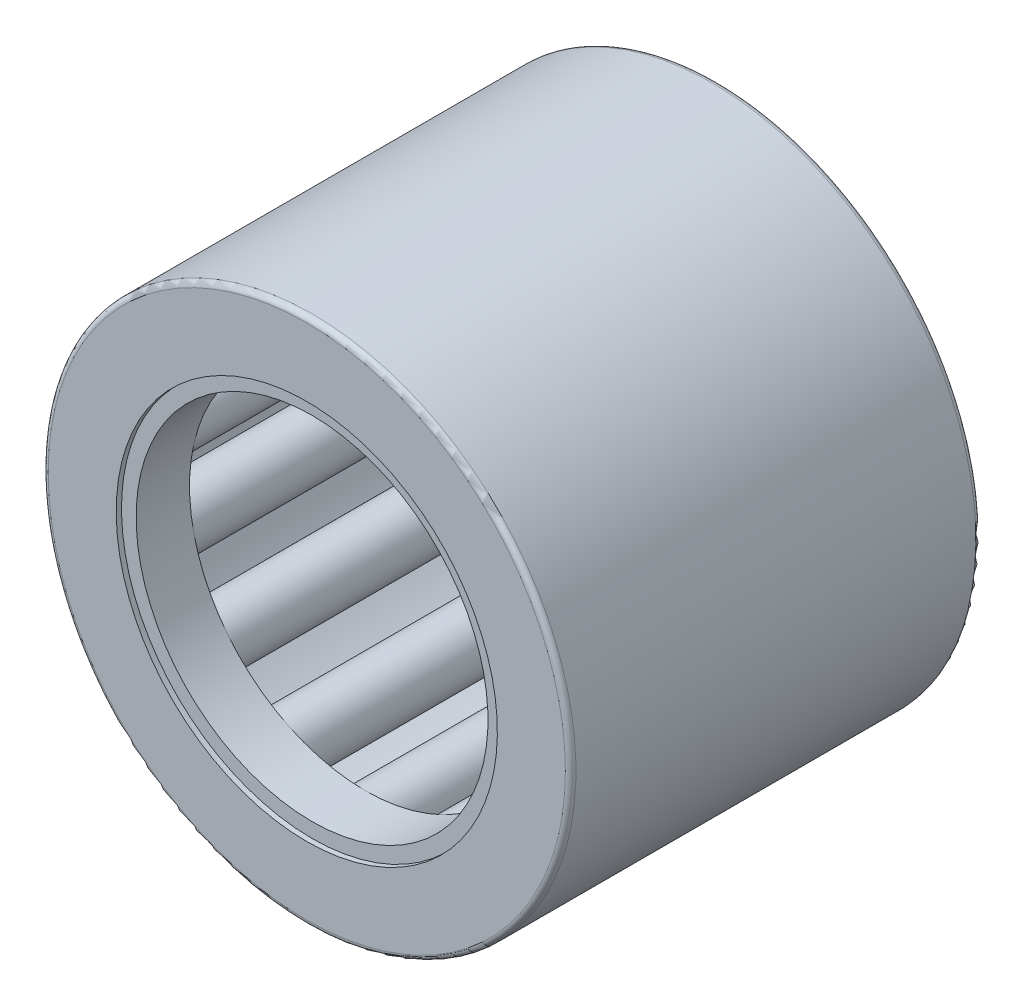
SolidWorks part; units mm, degrees
ref_plane "Front Plane" through (0, 0, 0) normal (0, 0, 1) x (1, 0, 0)
ref_plane "Top Plane" through (0, 0, 0) normal (0, 1, 0) x (1, 0, 0)
ref_plane "Right Plane" through (0, 0, 0) normal (1, 0, 0) x (0, 0, -1)
sketch "Sketch1" plane through (0, 0, 0) normal (1, 0, 0) x (0, 0, -1)
  line L0 (-7, 0) -> (7, 0) construction
  line L1 (0, 0) -> (0, 9) construction
  line L2 (-7, 0) -> (-7, 9) construction
  line L3 (-7, 9) -> (7, 9)
  line L4 (7, 9) -> (7, 0) construction
  line L5 (7, 0) -> (6, 0) construction
  line L6 (6, 0) -> (6, 8) construction
  line L7 (6, 8) -> (-6, 8)
  line L8 (-6, 8) -> (-6, 0) construction
  line L9 (-6, 0) -> (-7, 0) construction
  line L10 (-7, 9) -> (-7, 6.5)
  line L11 (-7, 6.5) -> (-6, 6.5)
  line L12 (-6, 6.5) -> (-6, 8)
  line L13 (6, 9) -> (6, 8) construction
  line L14 (6, 8) -> (6, 6.5)
  line L15 (6, 6.5) -> (7, 6.5)
  line L16 (7, 6.5) -> (7, 9)
  line L17 (6, 8) -> (6, 7) construction
  line L18 (6, 7) -> (6, 6) construction
  line L19 (6, -8) -> (6, -7) construction
  line L20 (6, -9) -> (6, -8) construction
  line L21 (7, -6.5) -> (7, -9) construction
  line L22 (6, -6.5) -> (7, -6.5) construction
  line L23 (6, -8) -> (6, -6.5) construction
  line L24 (-6, -6.5) -> (-6, -8) construction
  line L25 (-7, -6.5) -> (-6, -6.5) construction
  line L26 (-7, -9) -> (-7, -6.5) construction
  line L27 (6, -8) -> (-6, -8) construction
  line L28 (-7, -9) -> (7, -9) construction
  point P4 (0, 6)
  dimension "C | Width" = 14
  dimension "Fw | ID" = 12
  dimension "D | OD" = 18
sketch "Sketch7" plane through (0, 0, 0) normal (1, 0, 0) x (0, 0, -1)
  line L0 (-7, 9) -> (-7, 6.5) construction
  line L1 (-7, 6.5) -> (-6, 6.5) construction
  line L2 (-6, 6.5) -> (-6, 8) construction
  line L3 (6, 8) -> (-6, 8) construction
  line L4 (6, 8) -> (6, 6.5) construction
  line L5 (6, 6.5) -> (7, 6.5) construction
  line L6 (7, 6.5) -> (7, 9) construction
  line L8 (-7, 9) -> (7, 9) construction
  line L9 (-7, 9) -> (-7, 6.5)
  line L10 (-7, 6.5) -> (-6, 6.5)
  line L13 (-6, 6.5) -> (-6, 8)
  line L16 (6, 8) -> (-6, 8)
  line L17 (6, 8) -> (6, 6.5)
  line L18 (6, 6.5) -> (7, 6.5)
  line L19 (7, 6.5) -> (7, 9)
  line L20 (-7, 9) -> (7, 9)
revolve "Revolve1" add sketch "Sketch7" angle 360 about L0
sketch "Sketch2" plane through (0, 0, 0) normal (1, 0, 0) x (0, 0, -1)
  line L0 (-7, 6.5) -> (-6, 6.5) construction
  line L1 (-5, 7) -> (5, 7) construction
  line L2 (-5, 7) -> (-5, 8) construction
  line L3 (-5, 8) -> (5, 8)
  line L4 (5, 7) -> (5, 8) construction
  line L5 (6, 6.5) -> (7, 6.5) construction
  line L6 (-6, 7) -> (-5, 7) construction
  line L7 (5, 7) -> (6, 7) construction
  line L8 (7, 9) -> (7, 0) construction
  line L9 (-5, 7.25) -> (-5, 6.75) construction
  line L10 (-6, 7) -> (-6, 6.5) construction
  line L11 (-5, 8) -> (-5, 7.25)
  line L12 (5, 8) -> (5, 7.25)
  line L13 (5, 7.25) -> (-5, 7.25)
  line L14 (0, 8) -> (0, 6) construction
  line L16 (-5, 6.75) -> (-6, 6.75) construction
  line L17 (0, 0) -> (7, 0) construction
  line L18 (-5, -6.75) -> (-6, -6.75) construction
  line L19 (0, -8) -> (0, -6) construction
  line L20 (-6, -7) -> (-6, -6.5) construction
  line L21 (-5, -7.25) -> (-5, -6.75) construction
  line L22 (5, -7) -> (6, -7) construction
  line L23 (-6, -7) -> (-5, -7) construction
  line L24 (5, -7) -> (5, -8) construction
  line L25 (-5, -7) -> (-5, -8) construction
  line L26 (-5, -7) -> (5, -7) construction
  line L27 (5, -7.25) -> (-5, -7.25) construction
  line L28 (5, -8) -> (5, -7.25) construction
  line L29 (-5, -8) -> (-5, -7.25) construction
  line L30 (-5, -8) -> (5, -8) construction
  line L33 (6, 8) -> (-6, 8) construction
  line L34 (6, 8) -> (6, 6.5) construction
  line L35 (-6, 6.5) -> (-6, 8) construction
  line L36 (0, 0) -> (0, 9) construction
  point P16 (0, 7)
revolve "Revolve2" add sketch "Sketch2" angle 360 about L1
sketch "Sketch3" plane through (0, 0, 0) normal (1, 0, 0) x (0, 0, -1)
  line L1 (-6, 7) -> (6, 7)
  line L2 (-6, 7) -> (-6, 7.25)
  line L3 (-6, 7.25) -> (6, 7.25)
  line L4 (6, 7) -> (6, 7.25)
  line L5 (0, 0) -> (7, 0) construction
  line L7 (6, -7) -> (6, -7.25) construction
  line L8 (-6, -7.25) -> (6, -7.25) construction
  line L9 (-6, -7) -> (-6, -7.25) construction
  line L10 (-6, -7) -> (6, -7) construction
  line L11 (6, 8) -> (6, 6.5) construction
  line L12 (7, 9) -> (7, 0) construction
revolve "Revolve3" add sketch "Sketch3" angle 360 about L1
ref_axis "Axis1" through (0, 6.5, 7) along (0, 1, 0)
pattern_circular "CirPattern1" count 14 every 25.714 about axis through (0, 0, 7) along (0, 0, -1) of bodies 166 167
fillet "Fillet1" radius 0.18 2 edges at (0, -9, -7) (0, -9, 7)
sketch "Sketch4" plane through (0, 0, 0) normal (1, 0, 0) x (0, 0, -1)
  line L0 (5, 8) -> (5, 7.25) construction
  line L1 (6.82, 6) -> (5, 6)
  line L2 (6.82, 6) -> (6.82, 6.5)
  line L3 (6.82, 6.5) -> (5, 6.5)
  line L4 (5, 6) -> (5, 6.5)
  line L7 (6, 6.5) -> (7, 6.5) construction
  line L8 (6.82, -9) -> (6.82, 9) construction
revolve "Revolve4" add sketch "Sketch4" angle 360 about L0
sketch "Sketch5" plane through (0, 0, 0) normal (1, 0, 0) x (0, 0, -1)
  line L0 (-6.82, 9) -> (-6.82, -9) construction
  line L1 (-5, 6) -> (-6.82, 6)
  line L2 (-5, 6) -> (-5, 6.5)
  line L3 (-5, 6.5) -> (-6.82, 6.5)
  line L4 (-6.82, 6) -> (-6.82, 6.5)
  line L5 (-5, 8) -> (-5, 7.25) construction
  line L6 (-7, 6.5) -> (-6, 6.5) construction
revolve "Revolve5" add sketch "Sketch5" angle 360 about L0
sketch "Front View" plane through (0, 0, 0) normal (0, 0, 1) x (1, 0, 0)
  circle A0 centre (0, 0) radius 6 construction
  circle A1 centre (0, 0) radius 9 construction
  dimension "ID" = 12
  dimension "OD" = 18
sketch "Right View" plane through (0, 0, 0) normal (1, 0, 0) x (0, 0, -1)
  line L0 (-7, 9) -> (7, 9) construction
  line L1 (-7, 9) -> (7, 9) construction
  line L2 (0, 0) -> (0, 9) construction
  point P4 (0, 9)
  dimension "Width" = 14
equation "\"Rollers@CirPattern1\"  = \"OD@Sketch1\"*.75"
equation "\"D1@Fillet1\" = \"D | OD@Sketch1\" * .01"
equation "\"Angle@CirPattern1\"=360 / \"Rollers@CirPattern1\""
equation "\"ID@Front View\" = \"Fw | ID@Sketch1\""
equation "\"OD@Front View\" = \"D | OD@Sketch1\""
equation "\"Width@Right View\" = \"C | Width@Sketch1\""
